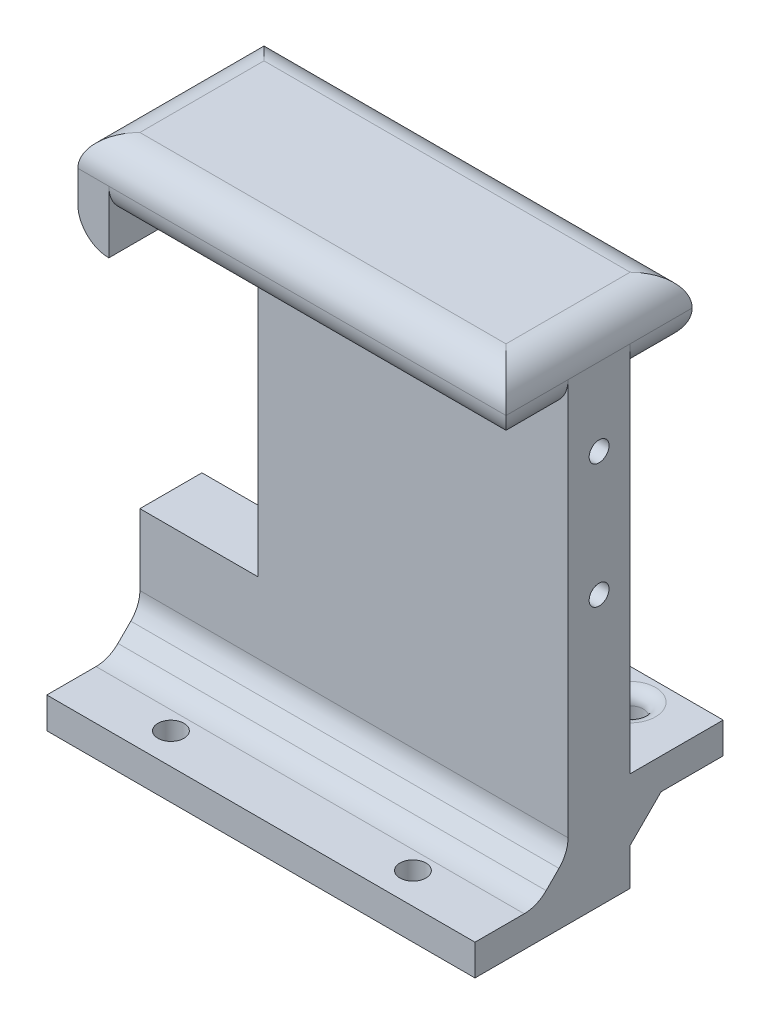
SolidWorks part; units mm, degrees
ref_plane "Plan de face" through (0, 0, 0) normal (0, 0, 1) x (1, 0, 0)
ref_plane "Plan de dessus" through (0, 0, 0) normal (0, 1, 0) x (1, 0, 0)
ref_plane "Plan de droite" through (0, 0, 0) normal (1, 0, 0) x (0, 0, -1)
sketch "Esquisse1" plane through (0, 0, 0) normal (0, 0, 1) x (1, 0, 0)
  line L0 (0, 0) -> (0, 81)
  line L1 (0, 81) -> (-69, 81)
  line L2 (-69, 81) -> (-69, 66)
  line L3 (-69, 66) -> (-64, 66)
  line L4 (-64, 66) -> (-64, 71)
  line L5 (-64, 71) -> (-50, 71)
  line L6 (-50, 71) -> (-50, 0)
  line L7 (-50, 0) -> (0, 0)
  dimension "D1" = 71
  dimension "D2" = 14
  dimension "D3" = 5
  dimension "D4" = 5
  dimension "D5" = 10
  dimension "D6" = 50
extrude "Boss.-Extru.1" add sketch "Esquisse1" along normal blind 10
sketch "Esquisse2" plane through (0, 0, 10) normal (0, 0, 1) x (1, 0, 0)
  line L0 (0, 0) -> (0, 81) construction
  line L1 (0, 71) -> (-69, 71)
  line L2 (0, 71) -> (0, 81)
  line L3 (0, 81) -> (-69, 81)
  line L4 (-69, 71) -> (-69, 81)
  line L5 (-64, 71) -> (-50, 71) construction
  dimension "D1" = 0
extrude "Boss.-Extru.2" add sketch "Esquisse2" along normal blind 10 and the other way blind 20
sketch "Esquisse4" plane through (0, 0, 10) normal (0, 0, 1) x (1, 0, 0)
  line L1 (-50, 0) -> (-69, 0)
  line L2 (-50, 0) -> (-50, 23.5058)
  line L3 (-50, 23.5058) -> (-69, 23.5058)
  line L4 (-69, 0) -> (-69, 23.5058)
  circle A0 centre (-57, 12) radius 4.1
  dimension "D2" = 7
  dimension "D3" = 8.2
  dimension "D4" = 12
  dimension "D1" = 19
extrude "Boss.-Extru.3" add sketch "Esquisse4" against normal up to surface (10 mm away) up to face at (-25, 35.5, 0)
sketch "Esquisse5" plane through (0, 71, 0) normal (0, -1, 0) x (1, 0, 0)
  line L0 (-69, -10) -> (0, -10) construction
  line L1 (-69, 20) -> (-64, 20)
  line L2 (-69, 20) -> (-69, -10)
  line L3 (-69, -10) -> (-64, -10)
  line L4 (-64, 20) -> (-64, -10)
  dimension "D1" = 0
  dimension "D2" = 5
extrude "Boss.-Extru.4" add sketch "Esquisse5" along normal up to surface (5 mm away) up to face at (-66.5, 66, 5)
sketch "Esquisse6" plane through (0, 0, 10) normal (0, 0, 1) x (1, 0, 0)
  line L0 (-69, 23.5058) -> (-69, 0) construction
  line L1 (0, 0) -> (-69, 0)
  line L2 (0, 0) -> (0, 5)
  line L3 (0, 5) -> (-69, 5)
  line L4 (-69, 0) -> (-69, 5)
  dimension "D1" = 5
extrude "Boss.-Extru.5" add sketch "Esquisse6" along normal blind 15
sketch "Esquisse7" plane through (0, 0, 10) normal (0, 0, 1) x (1, 0, 0)
  circle A0 centre (-57, 12) radius 5.4489
extrude "Boss.-Extru.6" add sketch "Esquisse7" against normal blind 5
chamfer "Chanfrein2" distance 5 angle 45 1 edges at (-34.5, 5, 10)
sketch "Esquisse8" plane through (0, 5, 0) normal (0, 1, 0) x (1, 0, 0)
  line L0 (0, -20) -> (-69, -20) construction
  line L1 (0, -25) -> (0, -15) construction
  line L2 (-69, -25) -> (-69, -15) construction
  circle A0 centre (-15, -20) radius 2.1
  circle A1 centre (-54, -20) radius 2.1
  dimension "D1" = 4.2
  dimension "D2" = 4.2
  dimension "D3" = 15
  dimension "D4" = 15
extrude "Enlèv. mat.-Extru.1" cut sketch "Esquisse8" against normal blind 5
sketch "Esquisse9" plane through (-50, 0, 0) normal (-1, 0, 0) x (0, 0, 1)
  line L0 (0, 23.5058) -> (10, 23.5058) construction
  line L4 (5, 63.5058) -> (5, 43.5058) construction
  circle A0 centre (5, 63.5058) radius 1.6
  circle A1 centre (5, 43.5058) radius 1.6
  point P0 (5, 53.5058)
  dimension "D1" = 3.2
  dimension "D2" = 3.2
  dimension "D3" = 20
  dimension "D4" = 30
extrude "Enlèv. mat.-Extru.2" cut sketch "Esquisse9" against normal blind 68
sketch "Esquisse10" plane through (0, 0, 0) normal (0, 0, -1) x (-1, 0, 0)
  line L3 (0, 16) -> (50, 16)
  line L6 (69, 0) -> (0, 0) construction
  line L7 (50, 16) -> (0, 16)
  line L8 (50, 16) -> (50, 11)
  line L9 (50, 11) -> (0, 11)
  line L10 (0, 16) -> (0, 11)
  line M5 (0, 71) -> (0, 0)
  dimension "D1" = 16
  dimension "D2" = 5
  dimension "D3" = 50
extrude "Boss.-Extru.7" add sketch "Esquisse10" along normal blind 15 contours L9 L8 L3 M5 region at (-25, 13.5, 0)
chamfer "Chanfrein3" distance 5 angle 45 1 edges at (-25, 11, 0)
sketch "Esquisse11" plane through (0, 16, 0) normal (0, 1, 0) x (1, 0, 0)
  line L0 (-50, 10) -> (0, 10) construction
  line L1 (-50, 15) -> (-50, 0) construction
  line L2 (0, 15) -> (0, 0) construction
  line L3 (0, 15) -> (-50, 15) construction
  circle A0 centre (-10, 10) radius 2.1
  circle A1 centre (-40, 10) radius 2.1
  dimension "D2" = 10
  dimension "D3" = 10
  dimension "D4" = 4.2
  dimension "D5" = 4.2
  dimension "D1" = 5
extrude "Enlèv. mat.-Extru.3" cut sketch "Esquisse11" against normal blind 10
fillet "Congé1" radius 2 2 edges at (-10, 16, -7.9) (-40, 16, -7.9)
fillet "Congé2" radius 5 11 edges at (-34.5, 10, 10) (-34.5, 5, 15) (-32, 71, -10) (0, 71, -5) (0, 71, 15) (-32, 71, 20) (-34.5, 81, 20) (-34.5, 81, -10) (0, 81, 5) (-69, 81, 5) (-69, 66, 5)
